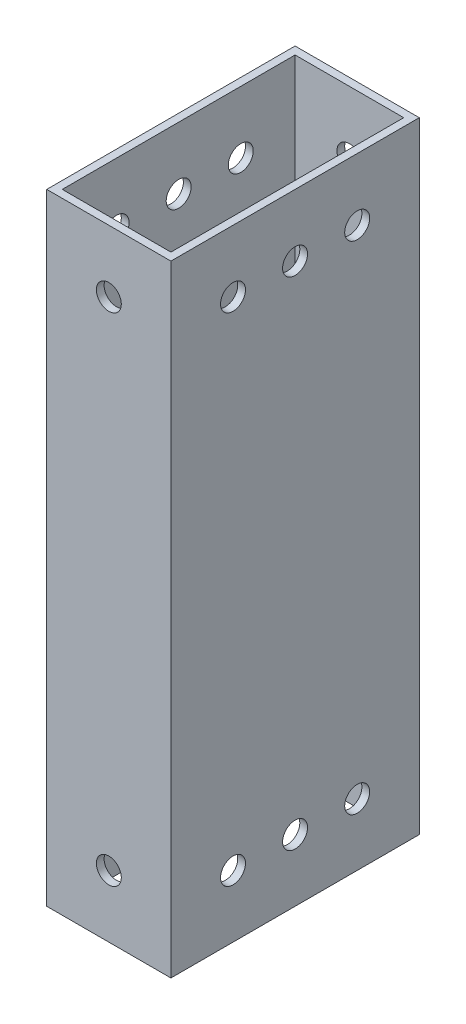
SolidWorks part; units mm, degrees
material "6061-T6 (SS)"
ref_plane "Front" through (0, 0, 0) normal (0, 0, 1) x (1, 0, 0)
ref_plane "Top" through (0, 0, 0) normal (0, 1, 0) x (1, 0, 0)
ref_plane "Right" through (0, 0, 0) normal (1, 0, 0) x (0, 0, -1)
sketch "Sketch1" plane through (0, 0, 0) normal (0, 1, 0) x (1, 0, 0)
  line L1 (12.7, 25.4) -> (-12.7, 25.4)
  line L2 (12.7, 25.4) -> (12.7, -25.4)
  line L3 (12.7, -25.4) -> (-12.7, -25.4)
  line L4 (-12.7, 25.4) -> (-12.7, -25.4)
  line L5 (12.7, 25.4) -> (-12.7, -25.4) construction
  line L6 (12.7, -25.4) -> (-12.7, 25.4) construction
  point P0 (0, 0)
  dimension "D1" = 25.4
  dimension "D2" = 50.8
extrude "Extrude-Thin1" add sketch "Sketch1" along normal up to surface (127 mm away) thin thin type one direction reverse wall 1.5875
sketch "Sketch4" plane through (-12.7, 0, 0) normal (-1, 0, 0) x (0, 0, 1)
  line L0 (-12.7, 12.7) -> (12.7, 12.7) construction
  line L3 (-12.7, 114.3) -> (12.7, 114.3) construction
  line L5 (-25.4, 0) -> (25.4, 0) construction
  line L6 (-25.4, 127) -> (25.4, 127) construction
  point P0 (-12.7, 114.3)
  point P2 (0, 114.3)
  point P4 (12.7, 114.3)
  point P6 (-12.7, 12.7)
  point P8 (0, 12.7)
  point P10 (12.7, 12.7)
  dimension "D1" = 12.7
  dimension "D2" = 12.7
  dimension "D3" = 12.7
  dimension "D4" = 12.7
hole_wizard "#10 Clearance Hole1" positions "Sketch4" profile "Sketch3" hole size "#10" standard "ANSI Inch" end condition through all
sketch "Sketch3" plane through (-12.7, 114.3, -12.7) normal (0, 1, 0) x (0, 0, 1)
  line L0 (0, 0) -> (0, 25.4)
  line L1 (0, 25.4) -> (2.5527, 25.4)
  line L2 (2.5527, 25.4) -> (2.5527, 0)
  line L5 (2.5527, 0) -> (0, 0)
  line L11 (0, -6.35) -> (0, 107.95) construction
  dimension "Thru Hole Dia." = 5.1054
  dimension "Thru Hole Depth" = 25.4
sketch "Sketch7" plane through (0, 0, 25.4) normal (0, 0, 1) x (1, 0, 0)
  line L0 (-12.7, 0) -> (12.7, 0) construction
  line L1 (-12.7, 127) -> (12.7, 127) construction
  point P0 (0, 12.7)
  point P2 (0, 114.3)
  dimension "D1" = 12.7
  dimension "D2" = 12.7
hole_wizard "#10 Clearance Hole2" positions "Sketch7" profile "Sketch6" hole size "#10" standard "ANSI Inch" end condition through all
sketch "Sketch6" plane through (0, 12.7, 25.4) normal (1, 0, 0) x (0, -1, 0)
  line L0 (0, 0) -> (0, 50.8)
  line L1 (0, 50.8) -> (2.5527, 50.8)
  line L2 (2.5527, 50.8) -> (2.5527, 0)
  line L5 (2.5527, 0) -> (0, 0)
  line L11 (0, -6.35) -> (0, 107.95) construction
  dimension "Thru Hole Dia." = 5.1054
  dimension "Thru Hole Depth" = 50.8
